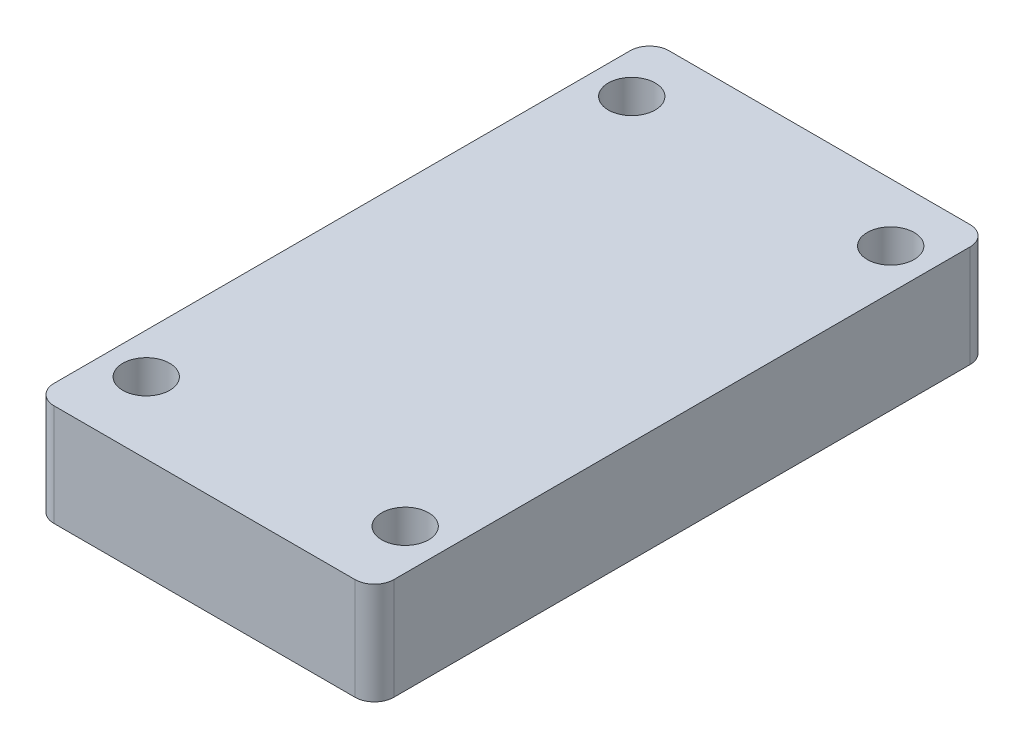
SolidWorks part; units mm, degrees
material "ABS"
ref_plane "前视基准面" through (0, 0, 0) normal (0, 0, 1) x (1, 0, 0)
ref_plane "上视基准面" through (0, 0, 0) normal (0, 1, 0) x (1, 0, 0)
ref_plane "右视基准面" through (0, 0, 0) normal (1, 0, 0) x (0, 0, -1)
sketch "草图1" plane through (0, 0, 0) normal (0, 1, 0) x (1, 0, 0)
  line L1 (10.5, -19) -> (-10.5, -19)
  line L2 (10.5, -19) -> (10.5, 19)
  line L3 (10.5, 19) -> (-10.5, 19)
  line L4 (-10.5, -19) -> (-10.5, 19)
  line L5 (10.5, -19) -> (-10.5, 19) construction
  line L6 (10.5, 19) -> (-10.5, -19) construction
  point P0 (0, 0)
  dimension "D1" = 21
  dimension "D2" = 38
extrude "凸台-拉伸1" add sketch "草图1" along normal blind 6.3
fillet "圆角1" radius 1.2 4 edges at (-10.5, 3.15, -19) (10.5, 3.15, -19) (-10.5, 3.15, 19) (10.5, 3.15, 19)
sketch "草图2" plane through (0, 6.3, 0) normal (0, 1, 0) x (1, 0, 0)
  line L0 (0, 0) -> (0, 0.4) construction
  line L1 (8, -14.6) -> (-8, -14.6) construction
  line L2 (8, -14.6) -> (8, 15.4) construction
  line L3 (8, 15.4) -> (-8, 15.4) construction
  line L4 (-8, -14.6) -> (-8, 15.4) construction
  line L5 (8, -14.6) -> (-8, 15.4) construction
  line L6 (8, 15.4) -> (-8, -14.6) construction
  line L7 (9.3, 19) -> (-9.3, 19) construction
  circle A0 centre (-8, 15.4) radius 1.45
  circle A1 centre (8, 15.4) radius 1.45
  circle A2 centre (-8, -14.6) radius 1.45
  circle A3 centre (8, -14.6) radius 1.45
  point P0 (0, 0.4)
  dimension "D4" = 2.9
  dimension "D1" = 16
  dimension "D2" = 30
  dimension "D3" = 3.6
extrude "切除-拉伸1" cut sketch "草图2" against normal through all
